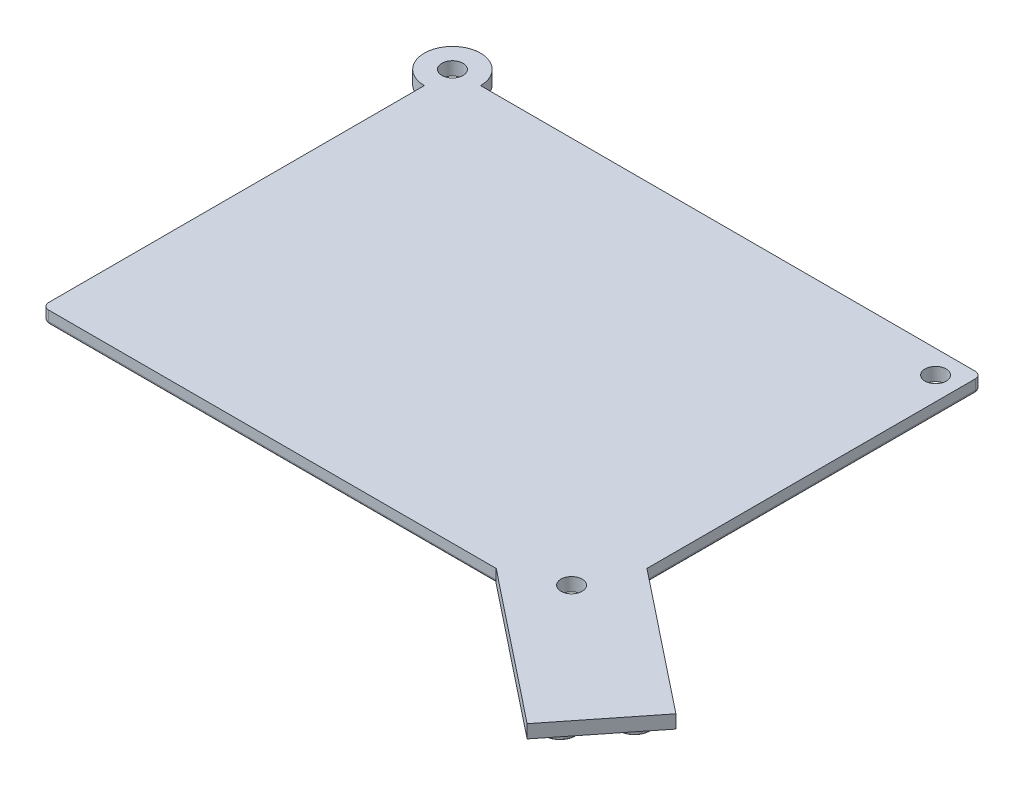
SolidWorks part; units mm, degrees
material "PVC Rigid"
ref_plane "Front Plane" through (0, 0, 0) normal (0, 0, 1) x (1, 0, 0)
ref_plane "Top Plane" through (0, 0, 0) normal (0, 1, 0) x (1, 0, 0)
ref_plane "Right Plane" through (0, 0, 0) normal (1, 0, 0) x (0, 0, -1)
sketch "Sketch1" plane through (0, 0, 0) normal (0, 1, 0) x (1, 0, 0)
  line L0 (40, -31) -> (-40, 31) construction
  line L1 (-40, -31) -> (40, -31)
  line L2 (-40, -31) -> (-40, 26.75)
  line L3 (-35.75, 31) -> (40, 31)
  line L4 (40, -31) -> (40, 31)
  line L5 (-40, -31) -> (40, 31) construction
  arc A5 (-35.75, 31) -> (-40, 26.75) centre (-40, 31) ccw
  point P0 (0, 0)
  point P6 (0, 0)
  point P7 (0, 0)
  dimension "D3" = 4.25
  dimension "D4" = 4.25
  dimension "D5" = 4.25
  dimension "D1" = 80
  dimension "D2" = 62
extrude "Main Body" add sketch "Sketch1" along normal blind 2
fillet "Corners" radius 1 3 edges at (-40, 1, 31) (40, 1, -31) (40, 1, 31)
fillet "Edge" radius 0.5 7 edges at (-39.7071, 0, 30.7071) (39.7071, 0, -30.7071) (39.7071, 0, 30.7071) (-40, 0, 1.625) (1.625, 0, -31) (40, 0, 0) (0, 0, 31)
sketch "Sketch8" plane through (0, 2, 0) normal (0, 1, 0) x (1, 0, 0)
  line L2 (40, -19.6117) -> (61.2107, -36.4473)
  line L3 (40, -30) -> (40, 30) construction
  line L5 (61.2107, -36.4473) -> (51.2636, -48.9794)
  line L6 (51.2636, -48.9794) -> (28.6117, -31)
  line L8 (-39, -31) -> (39, -31) construction
  line L9 (28.6117, -31) -> (40, -19.6117)
  line L10 (39, -30) -> (24.8579, -15.8579) construction
  line L11 (39, -30.5) -> (-39, -30.5) construction
  point P12 (24.4127, -31)
  point P13 (34.3059, -25.3059)
  point P14 (40, -16.911)
  point P15 (28.6117, -31)
  dimension "D1" = 45
  dimension "D2" = 20
  dimension "D3" = 16
  dimension "D4" = 28
extrude "DivingBoard" add sketch "Sketch8" against normal up to surface (2 mm away) up to face at (-0.2552, 0, -0.2552)
sketch "Sketch7" plane through (0, 0, 0) normal (0, -1, 0) x (-1, 0, 0)
  line L0 (39, -31) -> (-28.6117, -31) construction
  line L3 (-40, -19.6117) -> (-40, 30) construction
  line L4 (-39, 31) -> (35.75, 31) construction
  circle A0 centre (40, 31) radius 1.6
  circle A2 centre (-36.5, -27.5) radius 1.6
  circle A3 centre (-36.5, 27.5) radius 1.6
  arc A4 (39.5, 26.7795) -> (35.7795, 30.5) centre (40, 31) ccw construction
  dimension "D1" = 3.2
  dimension "D4" = 3.2
  dimension "D5" = 3.2
  dimension "D2" = 3.5
  dimension "D3" = 3.5
  dimension "D6" = 3.5
extrude "Lid Holes" cut sketch "Sketch7" against normal through all both and the other way through all
sketch "Sketch4" plane through (0, 0, 0) normal (0, -1, 0) x (-1, 0, 0)
  line L0 (-30, 24) -> (-30, -24) construction
  line L3 (-1.1, 0) -> (1.1, 0) construction
  line L4 (-40, -19.6117) -> (-40, 30) construction
  circle A0 centre (-30, 24) radius 2.325
  circle A1 centre (-30, 16) radius 2.325
  point P2 (-30, 0)
  point P8 (0, 0)
  dimension "D1" = 4.65
  dimension "D2" = 4.65
  dimension "D3" = 8
  dimension "D4" = 48
  dimension "D5" = 10
extrude "Boss-Extrude3" add sketch "Sketch4" along normal blind 1.6
fillet "Fillet3" radius 0.05 1 edges at (30, -1.6, -26.325)
pattern_linear "LPattern5" count 4 spacing 8 along (-1, 0, 0) of "Boss-Extrude3", "Fillet3"
sketch "LEGO straightline reference" plane through (0, 0, 0) normal (0, -1, 0) x (-1, 0, 0)
  line L0 (-30, 24) -> (-30, 16) construction
  line L1 (-30, 16) -> (-30, 20) construction
  line L2 (-30, 20) -> (-6, 20) construction
  line L3 (-6, 24) -> (-6, 16) construction
  point P10 (-6.0048, 19.7064)
sketch "Sketch10" plane through (0, 0, 0) normal (0, -1, 0) x (-1, 0, 0)
  line L0 (-56.2371, -42.7133) -> (-31.1728, -22.8191) construction
  line L1 (-61.2107, -36.4473) -> (-51.2636, -48.9794) construction
  line L2 (-55.5909, -37.0935) -> (-50.6173, -43.3596) construction
  circle A0 centre (-55.5909, -37.0935) radius 2.325
  circle A1 centre (-50.6173, -43.3596) radius 2.325
  point P5 (-56.2371, -42.7133)
  point P9 (-53.1041, -40.2266)
  dimension "D2" = 4.65
  dimension "D3" = 4.65
  dimension "D1" = 32
  dimension "D4" = 8
  dimension "D5" = 4
extrude "Pegs (Diagonal)" add sketch "Sketch10" along normal blind 1.6
fillet "Fillet4" radius 0.05 2 edges at (50.6173, -1.6, 41.0346) (55.5909, -1.6, 34.7685)
pattern_linear "LPattern6" count 4 spacing 8 along (-0.7833, 0, -0.6217) of "Fillet4", "Pegs (Diagonal)"
equation "\"D3@Sketch7\"=\"D2@Sketch7\""
equation "\"D4@Sketch7\"=\"D1@Sketch7\""
equation "\"D5@Sketch7\"=\"D1@Sketch7\""
equation "\"D2@Sketch4\"=\"D1@Sketch4\""
equation "\"D3@Sketch10\"=\"D2@Sketch10\""
